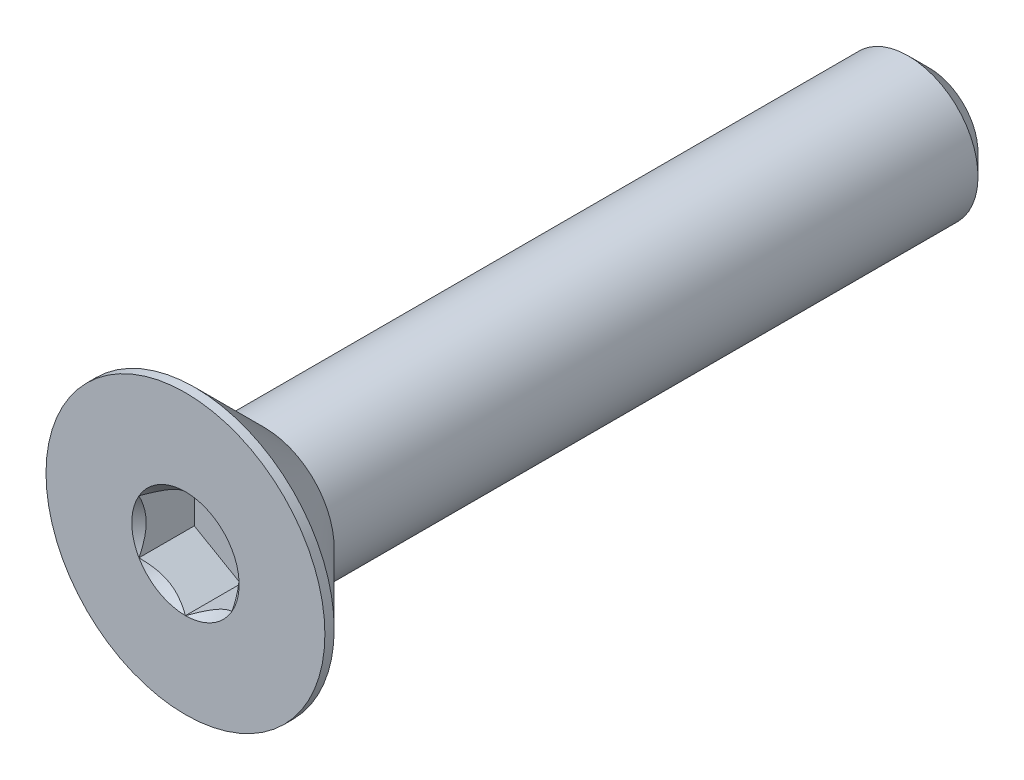
SolidWorks part; units mm, degrees
material "Alloy Steel"
ref_plane "Front" through (0, 0, 0) normal (0, 0, 1) x (1, 0, 0)
ref_plane "Top" through (0, 0, 0) normal (0, 1, 0) x (1, 0, 0)
ref_plane "Right" through (0, 0, 0) normal (1, 0, 0) x (0, 0, -1)
ref_axis "Central Axis" through (0, 0, -89.2244) along (0, 0, 1)
sketch "Sketch1" plane through (0, 0, 0) normal (1, 0, 0) x (0, 0, -1)
  line L0 (-8, 3) -> (-7.8, 3) construction
  line L1 (-7.8, 3) -> (-6.3, 1.5) construction
  line L2 (-8, 1.5) -> (8, 1.5) construction
  line L3 (8, 1.5) -> (8, 0) construction
  line L4 (8, 0) -> (-8, 0) construction
  line L5 (-8, 0) -> (-8, 3) construction
  line L6 (-8, 3) -> (-8, -3) construction
  line L7 (8, 1.5) -> (8, -1.5) construction
  line L8 (-8, -3) -> (-7.8, -3) construction
  line L9 (-7.8, -3) -> (-6.3, -1.5) construction
  line L11 (-8, 1.5) -> (-8, 0) construction
  line L12 (-6.3, 1.5) -> (-6.3, 0) construction
  line L13 (7.9688, 1.5541) -> (8.2188, 1.1211) construction
  line L14 (8.2188, 1.1211) -> (8.4687, 1.5541) construction
  line L15 (8.4687, 1.5541) -> (7.9688, 1.5541) construction
  line L16 (8.2188, 1.5541) -> (8.2188, 1.5) construction
  line L17 (8.2188, 1.5) -> (8.2188, 1.1752) construction
  line L18 (8.2188, 1.1752) -> (8.2188, 1.1211) construction
  line L19 (8.2188, 1.5271) -> (8.4531, 1.5271) construction
  line L20 (8.2188, 1.5271) -> (7.9844, 1.5271) construction
  line L21 (8, 1.5) -> (8.4375, 1.5) construction
  line L22 (8.1875, 1.1752) -> (8.25, 1.1752) construction
  line L23 (8, -1.5) -> (-6.3, -1.5) construction
  point P10 (6.75, -1.5)
  point P24 (-6.3, 1.5)
  point P30 (0, 0)
  dimension "Head Diameter" = 6
  dimension "Head Height" = 1.7
  dimension "Length" = 16
  dimension "Countersink Angle" = 90
  dimension "Thread Pitch" = 0.5
  dimension "D2" = 0.0625
  dimension "Minimum Thread Length" = 14.3
  dimension "Thread Size" = 3
  dimension "D1" = 1.25
sketch "Sketch2" plane through (0, 0, 0) normal (0, 0, 1) x (1, 0, 0)
  line L1 (0, 1.1547) -> (-1, 0.5774) construction
  line L2 (-1, 0.5774) -> (-1, -0.5774) construction
  line L3 (-1, -0.5774) -> (0, -1.1547) construction
  line L4 (0, -1.1547) -> (1, -0.5774) construction
  line L5 (1, -0.5774) -> (1, 0.5774) construction
  line L6 (1, 0.5774) -> (0, 1.1547) construction
  circle A0 centre (0, 0) radius 1 construction
  dimension "Drive Size" = 2
sketch "Sketch3" plane through (0, 0, 0) normal (1, 0, 0) x (0, 0, -1)
  line L0 (-8, 1.5) -> (8, 1.5)
  line L1 (8, 1.5) -> (8, 0)
  line L2 (8, 0) -> (-8, 0)
  line L3 (-8, 0) -> (-8, 1.5)
revolve "Revolve1" add sketch "Sketch3" angle 360 about L4
chamfer "Chamfer1" distance 0.45 angle 45 1 edges at (0, 1.5, -8)
sketch "Sketch6" plane through (0, 0, 0) normal (1, 0, 0) x (0, 0, -1)
  line L0 (-8, 3) -> (-7.8, 3)
  line L1 (-7.8, 3) -> (-6.3, 1.5)
  line L2 (-6.3, 1.5) -> (-6.3, 0)
  line L3 (-6.3, 0) -> (-8, 0)
  line L4 (-8, 0) -> (-8, 3)
revolve "Revolve2" add sketch "Sketch6" angle 360 about L4
sketch "Sketch8" plane through (0, 0, 8) normal (0, 0, 1) x (1, 0, 0)
  line L0 (0, 1.1547) -> (-1, 0.5774) construction
  line L1 (1, 0.5774) -> (0, 1.1547) construction
  line L2 (1, -0.5774) -> (1, 0.5774) construction
  line L3 (0, -1.1547) -> (1, -0.5774) construction
  line L4 (-1, 0.5774) -> (-1, -0.5774) construction
  line L5 (-1, -0.5774) -> (0, -1.1547) construction
  line L6 (0, 1.1547) -> (-1, 0.5774)
  line L7 (1, 0.5774) -> (0, 1.1547)
  line L8 (1, -0.5774) -> (1, 0.5774)
  line L9 (0, -1.1547) -> (1, -0.5774)
  line L10 (-1, 0.5774) -> (-1, -0.5774)
  line L11 (-1, -0.5774) -> (0, -1.1547)
extrude "Cut-Extrude1" cut sketch "Sketch8" against normal blind 1.19
sketch "Sketch9" plane through (0, 0, 8) normal (0, 0, 1) x (1, 0, 0)
  circle A0 centre (0, 0) radius 1.1547
extrude "Cut-Extrude2" cut sketch "Sketch9" against normal up to next (1.19 mm away) draft 45
ref_plane "Plane1" [suppressed] through (0, 0, 6.3) normal (0, 0, 1) x (1, 0, 0)
split "Split1" [suppressed] bodies to split 124
sketch "Sketch4" [suppressed] plane through (0, 0, -8) normal (0, 0, -1) x (-1, 0, 0)
  circle A0 centre (0, 0) radius 1.5 construction
  circle A1 centre (0, 0) radius 1.5
curve "Helix/Spiral1" [suppressed] pitch 0.5 height 14.8 turns 29.6
sketch "Sketch10" [suppressed] plane through (0, 0, 0) normal (1, 0, 0) x (0, 0, -1)
  line L0 (7.9844, 1.5271) -> (8.4531, 1.5271)
  line L1 (8.4531, 1.5271) -> (8.25, 1.1752)
  line L2 (8.25, 1.1752) -> (8.1875, 1.1752)
  line L3 (8.1875, 1.1752) -> (7.9844, 1.5271)
sweep "Cut-Sweep1" [suppressed] cut profiles "Sketch10" path "Helix/Spiral1"
equation "\"D2@Sketch1\" = \"Thread Pitch@Sketch1\" / 8"
equation "\"D4@Helix/Spiral1\"=\"Thread Pitch@Sketch1\""
equation "\"D3@Helix/Spiral1\"=\"Minimum Thread Length@Sketch1\"+\"Thread Pitch@Sketch1\""
equation "\"D1@Chamfer1\"=\"Thread Size@Sketch1\"*.15"
equation "\"D1@Cut-Extrude1\"=\"Head Height@Sketch1\"*.7"
equation "\"D1@Sketch1\"=\"Thread Pitch@Sketch1\"*2.5"
